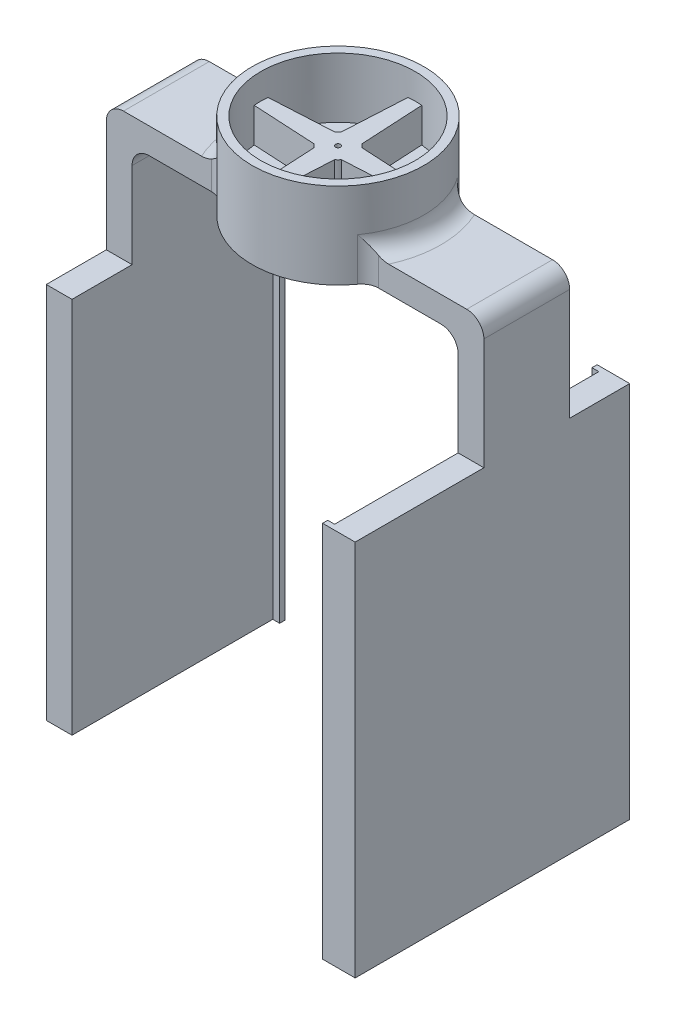
SolidWorks part; units mm, degrees
ref_plane "Front Plane" through (0, 0, 0) normal (0, 0, 1) x (1, 0, 0)
ref_plane "Top Plane" through (0, 0, 0) normal (0, 1, 0) x (1, 0, 0)
ref_plane "Right Plane" through (0, 0, 0) normal (1, 0, 0) x (0, 0, -1)
sketch "Sketch1" plane through (0, 0, 0) normal (0, 1, 0) x (1, 0, 0)
  circle A0 centre (0, 0) radius 25
  dimension "D1" = 50
extrude "Boss-Extrude1" add sketch "Sketch1" along normal blind 25
sketch "Sketch9" plane through (0, 0, 0) normal (1, 0, 0) x (0, 0, -1)
  line L0 (-25, 0) -> (25, 0) construction
  line L1 (-12.5, 0) -> (12.5, 0)
  line L2 (-12.5, 0) -> (-12.5, 7.5)
  line L3 (-12.5, 7.5) -> (12.5, 7.5)
  line L4 (12.5, 0) -> (12.5, 7.5)
  dimension "D1" = 12.5
  dimension "D2" = 25
  dimension "D3" = 7.5
extrude "Boss-Extrude3" add sketch "Sketch9" along normal blind 55 and the other way blind 55
sketch "Sketch16" plane through (0, 25, 0) normal (0, 1, 0) x (1, 0, 0)
  circle A0 centre (0, 0) radius 22.5
  dimension "D1" = 45
extrude "Cut-Extrude3" cut sketch "Sketch16" against normal blind 7.5
sketch "Sketch17" plane through (0, 17.5, 0) normal (0, 1, 0) x (1, 0, 0)
  line L0 (-3, 4) -> (-2, 22.4109)
  line L1 (0, -2.7417) -> (0, 10.4941) construction
  line L2 (3, 4) -> (2, 22.4109)
  line L3 (4, 3) -> (22.4109, 2)
  line L4 (4, -3) -> (22.4109, -2)
  line L5 (3, -4) -> (2, -22.4109)
  line L6 (-3, -4) -> (-2, -22.4109)
  line L7 (-4, -3) -> (-22.4109, -2)
  line L8 (-4, 3) -> (-22.4109, 2)
  circle A0 centre (0, 0) radius 5
  circle A1 centre (0, 0) radius 22.5
  circle A2 centre (0, 0) radius 0.75
  point P26 (0, 0)
  circle M6 centre (0, 0) radius 22.5
  dimension "D1" = 1.5
  dimension "D2" = 10
  dimension "D3" = 45
  dimension "D4" = 3
  dimension "D5" = 2
  dimension "D6" = 4
extrude "Cut-Extrude4" cut sketch "Sketch17" against normal blind 10 contours A0 L0 L8 M6 | A0 L3 L2 M6 | A0 L5 L4 M6 | A0 L7 L6 M6 | L1 A2 | A2 L1 region at (-10.7877, 17.5, -10.7877) region at (0.3183, 17.5, 0) region at (-0.3183, 17.5, 0) region at (10.7877, 17.5, -10.7877) region at (-10.7877, 17.5, 10.7877) region at (10.7877, 17.5, 10.7877)
sketch "Sketch22" plane through (0, 0, 0) normal (0, -1, 0) x (1, 0, 0)
  line L0 (-55, -12.5) -> (-21.6506, -12.5) construction
  line L1 (-55, 12.5) -> (-47.5, 12.5)
  line L2 (-55, 12.5) -> (-55, -12.5)
  line L3 (-55, -12.5) -> (-47.5, -12.5)
  line L4 (-47.5, 12.5) -> (-47.5, -12.5)
  dimension "D1" = 7.5
extrude "Boss-Extrude7" add sketch "Sketch22" along normal blind 30
sketch "Sketch23" plane through (0, -30, 0) normal (0, -1, 0) x (1, 0, 0)
  line L0 (-55, 12.5) -> (-55, -12.5) construction
  line L1 (-55, 30) -> (-47.5, 30)
  line L2 (-55, 30) -> (-55, -30)
  line L3 (-55, -30) -> (-47.5, -30)
  line L4 (-47.5, 30) -> (-47.5, -30)
  line L5 (-47.5, -12.5) -> (-47.5, 12.5) construction
  dimension "D1" = 60
  dimension "D2" = 30
extrude "Boss-Extrude8" add sketch "Sketch23" along normal blind 110
mirror "Mirror1" about plane through (0, 0, 0) normal (1, 0, 0) of "Boss-Extrude7"
sketch "Sketch24" plane through (0, -30, 0) normal (0, -1, 0) x (1, 0, 0)
  line L0 (55, 12.5) -> (55, -12.5) construction
  line L1 (47.5, 50) -> (55, 50)
  line L2 (47.5, 50) -> (47.5, -30)
  line L3 (47.5, -30) -> (55, -30)
  line L4 (55, 50) -> (55, -30)
  line L5 (47.5, -12.5) -> (47.5, 12.5) construction
  dimension "D1" = 30
  dimension "D2" = 50
extrude "Boss-Extrude9" add sketch "Sketch24" along normal blind 110
sketch "Sketch25" plane through (-47.5, 0, 0) normal (1, 0, 0) x (0, 0, -1)
  line L0 (30, -30) -> (12.5, -30) construction
  line L1 (28.5, -30) -> (30, -30)
  line L2 (28.5, -30) -> (28.5, -140)
  line L3 (28.5, -140) -> (30, -140)
  line L4 (30, -30) -> (30, -140)
  dimension "D1" = 1.5
extrude "Boss-Extrude10" add sketch "Sketch25" along normal blind 2
sketch "Sketch26" plane through (47.5, 0, 0) normal (-1, 0, 0) x (0, 0, 1)
  line L0 (50, -140) -> (-30, -140) construction
  line L1 (-30, -30) -> (-28.5, -30)
  line L2 (-30, -30) -> (-30, -140)
  line L3 (-30, -140) -> (-28.5, -140)
  line L4 (-28.5, -30) -> (-28.5, -140)
  line L5 (50, -30) -> (12.5, -30) construction
  line L6 (48.5, -30) -> (50, -30)
  line L7 (48.5, -30) -> (48.5, -140)
  line L8 (48.5, -140) -> (50, -140)
  line L9 (50, -30) -> (50, -140)
  dimension "D1" = 1.5
  dimension "D2" = 1.5
extrude "Boss-Extrude11" add sketch "Sketch26" along normal blind 2
fillet "Fillet6" radius 5 10 edges at (55, 7.5, 0) (-55, 7.5, 0) (-47.5, 0, 0) (47.5, 0, 0) (25, 7.5, 0) (-25, 7.5, 0) (-21.6506, 3.75, 12.5) (21.6506, 3.75, 12.5) (-21.6506, 3.75, -12.5) (21.6506, 3.75, -12.5)
